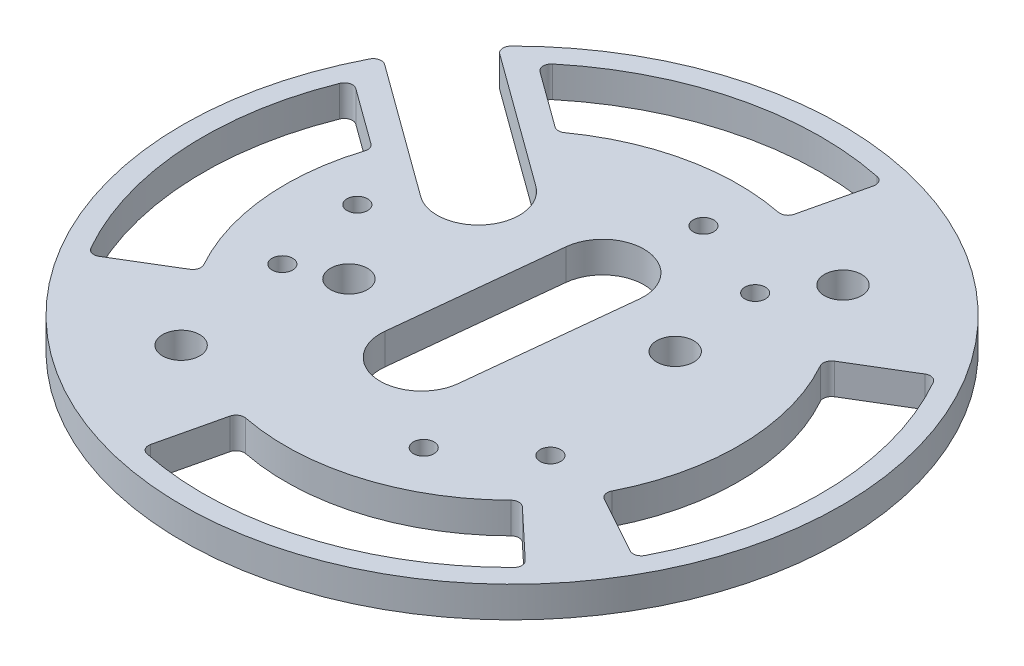
SolidWorks part; units mm, degrees
ref_plane "Front Plane" through (0, 0, 0) normal (0, 0, 1) x (1, 0, 0)
ref_plane "Top Plane" through (0, 0, 0) normal (0, 1, 0) x (1, 0, 0)
ref_plane "Right Plane" through (0, 0, 0) normal (1, 0, 0) x (0, 0, -1)
sketch "Sketch1" plane through (0, 0, 0) normal (0, 1, 0) x (1, 0, 0)
  circle A0 centre (0, 0) radius 101.6
extrude "Boss-Extrude1" add sketch "Sketch1" along normal blind 9.525
sketch "Sketch2" plane through (0, 9.525, 0) normal (0, 1, 0) x (1, 0, 0)
  line L0 (0, 0) -> (34.8175, 15.4709)
  line L1 (0, 60.325) -> (12.6294, 58.9882)
  line L2 (0, 60.325) -> (12.6294, 58.9882)
  line L3 (0, 60.325) -> (-1.3368, 47.6956)
  line L4 (12.6294, 58.9882) -> (11.2926, 46.3587)
  line L5 (-1.3368, 47.6956) -> (11.2926, 46.3587)
  line L6 (0, 0) -> (-34.8175, -15.4709)
  line L7 (0, 0) -> (5.6463, 53.3419)
  line L8 (5.6463, 53.3419) -> (6.6842, 63.1472)
  line L9 (6.6842, 63.1472) -> (6.9516, 65.6731)
  line L10 (0, 0) -> (5.6463, 53.3419)
  line L11 (6.6842, 63.1472) -> (6.9516, 65.6731)
  line L12 (6.9516, 65.6731) -> (10.6947, 101.0356)
  line L13 (4.9779, 47.0271) -> (-2.6737, -25.2589)
  line L14 (-2.6737, -25.2589) -> (2.6737, 25.2589) construction
  line L15 (-15.3031, -23.922) -> (-9.9558, 26.5957)
  line L16 (9.9558, -26.5957) -> (15.3031, 23.922)
  line L17 (0, 0) -> (5.6463, 53.3419) construction
  line L18 (0, 60.325) -> (11.2926, 46.3587)
  line L19 (12.6294, 58.9882) -> (-1.3368, 47.6956)
  line L20 (0, 0) -> (31.5608, 43.3723) construction
  line L21 (0, 0) -> (-53.3419, 5.6463) construction
  line L22 (0, 0) -> (-43.3723, 31.5608) construction
  line L23 (-48.5068, 35.297) -> (-38.2378, 27.8245) construction
  line L24 (-41.0343, 45.566) -> (-30.7653, 38.0935)
  line L25 (-55.9792, 25.028) -> (-45.7102, 17.5555)
  line L26 (-41.0343, 45.566) -> (-87.237, 79.1864)
  line L27 (-45.7102, 17.5555) -> (-104.486, 60.325)
  line L28 (-104.486, 60.325) -> (-87.237, 79.1864)
  circle A0 centre (0, 0) radius 63.5
  circle A1 centre (0, 0) radius 60.325
  circle A2 centre (0, 0) radius 25.4
  arc A3 (-15.3031, -23.922) -> (9.9558, -26.5957) centre (-2.6737, -25.2589) ccw
  arc A4 (15.3031, 23.922) -> (-9.9558, 26.5957) centre (2.6737, 25.2589) ccw
  circle A5 centre (5.6463, 53.3419) radius 3.175
  circle A6 centre (43.3723, -31.5608) radius 3.175
  circle A7 centre (-49.0186, -21.7811) radius 3.175
  circle A8 centre (0, 0) radius 53.6399
  circle A9 centre (31.5608, 43.3723) radius 3.175
  circle A10 centre (21.7811, -49.0186) radius 3.175
  circle A11 centre (-53.3419, 5.6463) radius 3.175
  circle A12 centre (-43.3723, 31.5608) radius 3.175
  arc A13 (-41.0343, 45.566) -> (-55.9792, 25.028) centre (-48.5068, 35.297) ccw
  arc A14 (-45.7102, 17.5555) -> (-30.7653, 38.0935) centre (-38.2378, 27.8245) ccw
  circle A17 centre (0, 0) radius 38.1
  circle A18 centre (-34.8175, -15.4709) radius 4.7625
  circle A19 centre (34.8175, 15.4709) radius 4.7625
  circle A20 centre (0, 0) radius 101.6 construction
  circle A21 centre (10.6947, 101.0356) radius 35.56
  circle A22 centre (-10.6947, -101.0356) radius 35.56
  point P11 (0, 0)
  point P20 (0, 0)
  point P38 (0, 0)
  point P39 (0, 0)
  point P40 (-43.3723, 31.5608)
  point P43 (0, 0)
  point P46 (0, 0)
  point P51 (0, 0)
  point P55 (0, 0)
  point P62 (0, 0)
  point P73 (0, 0)
  circle M1 centre (0, 0) radius 101.6
  dimension "D1" = 3
  dimension "D2" = 2
  dimension "D3" = 2
  dimension "D4" = 30
  dimension "D7" = 30
  dimension "D5" = 3
  dimension "D6" = 2
extrude "Cut-Extrude1" cut sketch "Sketch2" against normal blind 22.86 contours A8 A12 | A8 A12 | A13 A0 L26 L27 M1 | A13 A0 L27 | A13 L26 A0
sketch "Sketch3" plane through (0, 9.525, 0) normal (0, 1, 0) x (1, 0, 0)
  line L0 (0, 0) -> (34.8175, 15.4709)
  line L1 (34.8175, 15.4709) -> (63.8321, 28.3634)
  line L2 (63.8321, 28.3634) -> (87.0438, 38.6774)
  line L3 (0, 0) -> (91.1964, 27.4914)
  line L4 (0, 0) -> (81.5264, 49.2545)
  line L5 (0, 0) -> (69.4065, -65.2327)
  line L6 (0, 0) -> (83.4189, -45.9767)
  line L7 (0, 0) -> (-21.7899, -92.7241)
  line L8 (0, 0) -> (1.8925, -95.2312)
  line L9 (0, 0) -> (-91.1964, -27.4914)
  line L10 (0, 0) -> (-81.5264, -49.2545)
  line L11 (0, 0) -> (-69.4065, 65.2327)
  line L12 (0, 0) -> (-83.4189, 45.9767)
  line L13 (0, 0) -> (21.7899, 92.7241)
  line L14 (0, 0) -> (-1.8925, 95.2312)
  line L15 (-88.9801, 49.0418) -> (-45.7102, 17.5555) construction
  line L17 (-88.9801, 49.0418) -> (-52.4002, 22.4237)
  line L18 (-88.9801, 49.0418) -> (-93.4636, 42.8804)
  line L19 (-52.4002, 22.4237) -> (-56.8837, 16.2623)
  line L20 (-93.4636, 42.8804) -> (-56.8837, 16.2623)
  line L21 (-70.6637, 67.1265) -> (-37.3437, 42.8804)
  line L22 (-70.6637, 67.1265) -> (-66.1802, 73.2879)
  line L23 (-37.3437, 42.8804) -> (-32.8602, 49.0418)
  line L24 (-66.1802, 73.2879) -> (-32.8602, 49.0418)
  line L25 (-74.0352, 69.5798) -> (-30.7653, 38.0935) construction
  line L26 (0, 0) -> (-94.7208, 10.0263)
  circle A0 centre (0, 0) radius 63.5
  circle A1 centre (0, 0) radius 69.85
  circle A2 centre (0, 0) radius 95.25
  circle A3 centre (0, 0) radius 73.025
  circle A4 centre (-72.6193, 7.6868) radius 4.7625
  circle A5 centre (72.6193, -7.6868) radius 4.7625
  circle A6 centre (-29.6527, 66.7336) radius 4.7625
  circle A7 centre (42.9667, 59.0467) radius 4.7625
  circle A8 centre (72.6193, -7.6868) radius 4.7625
  circle A9 centre (29.6527, -66.7336) radius 4.7625
  circle A10 centre (-42.9667, -59.0467) radius 4.7625
  point P26 (0, 0)
  point P46 (0, 0)
  point P54 (0, 0)
  dimension "D1" = 6
  dimension "D2" = 2
  dimension "D3" = 6
extrude "Cut-Extrude2" cut sketch "Sketch3" against normal through all contours A6 A3 L14 A2 L24 | A3 A6 | A1 A6 A3 | A6 A3 L24 A1 | A6 A1 L14 A3 | A5 A3 L6 A2 L3 | A5 A3 L3 A1 | A3 A5 A1 | A3 A5 | A5 A1 L6 A3 | A9 A3 L8 A2 L5 | A3 A9 | A9 A1 L8 A3 | A3 A9 A1 | A9 A3 L5 A1 | A1 A10 | A3 A10 A1 | A3 A10 | A4 L26 A2 L9 A3 | A4 A3 L9 A1 | L26 A4 A3 | A3 A4 A1 L26 | A1 A4 A3 L26 | A3 A4 L26 | A4 A3 L20 A2 L26 | A4 A1 L20 A3 | A3 A7 | A1 A7 A3 | A1 A7 | A3 L13 A2 L14 | L13 A3 L14 A1 | A3 L2 A2 L4 | A3 L3 A2 L2 | L2 A3 L4 A1 | L3 A3 L2 A1 | A3 L7 A2 L8 | L7 A3 L8 A1 | L9 A3 L10 A1 | A3 L9 A2 L10
fillet "Fillet1" radius 2.54 2 edges at (-74.0352, 4.7625, -69.5798) (-88.9801, 4.7625, -49.0418)
fillet "Fillet3" radius 2.54 16 edges at (-87.2004, 4.7625, -38.3229) (-65.9927, 4.7625, -22.8907) (-59.786, 4.7625, 36.12) (-81.5264, 4.7625, 49.2545) (-15.9793, 4.7625, 67.9977) (-21.7899, 4.7625, 92.7241) (69.4065, 4.7625, 65.2327) (50.8981, 4.7625, 47.8373) (83.4189, 4.7625, 45.9767) (61.1738, 4.7625, 33.7162) (59.786, 4.7625, -36.12) (81.5264, 4.7625, -49.2545) (21.7899, 4.7625, -92.7241) (15.9793, 4.7625, -67.9977) (-42.0809, 4.7625, -55.7515) (-63.2886, 4.7625, -71.1837)
sketch "Sketch4" plane through (0, 9.525, 0) normal (0, 1, 0) x (1, 0, 0)
  circle A0 centre (42.9667, 59.0467) radius 5.715
  circle A1 centre (-42.9667, -59.0467) radius 5.715
  circle A2 centre (-34.8175, -15.4709) radius 5.715
  circle A3 centre (34.8175, 15.4709) radius 5.715
extrude "Cut-Extrude3" cut sketch "Sketch4" against normal blind 17.78 contours A0 | A3 | A2 | A1
